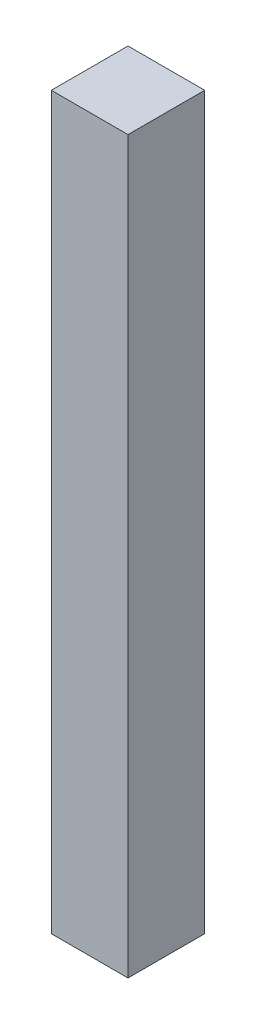
SolidWorks part; units mm, degrees
material "6061 Alloy"
ref_plane "Front Plane" through (0, 0, 0) normal (0, 0, 1) x (1, 0, 0)
ref_plane "Top Plane" through (0, 0, 0) normal (0, 1, 0) x (1, 0, 0)
ref_plane "Right Plane" through (0, 0, 0) normal (1, 0, 0) x (0, 0, -1)
sketch "Sketch1" plane through (0, 0, 0) normal (0, 1, 0) x (1, 0, 0)
  line L1 (-3.15, 3.15) -> (3.15, 3.15)
  line L2 (-3.15, 3.15) -> (-3.15, -3.15)
  line L3 (-3.15, -3.15) -> (3.15, -3.15)
  line L4 (3.15, 3.15) -> (3.15, -3.15)
  line L5 (-3.15, 3.15) -> (3.15, -3.15) construction
  line L6 (-3.15, -3.15) -> (3.15, 3.15) construction
  point P0 (0, 0)
  dimension "D1" = 6.3
extrude "Boss-Extrude1" add sketch "Sketch1" along normal blind 60
